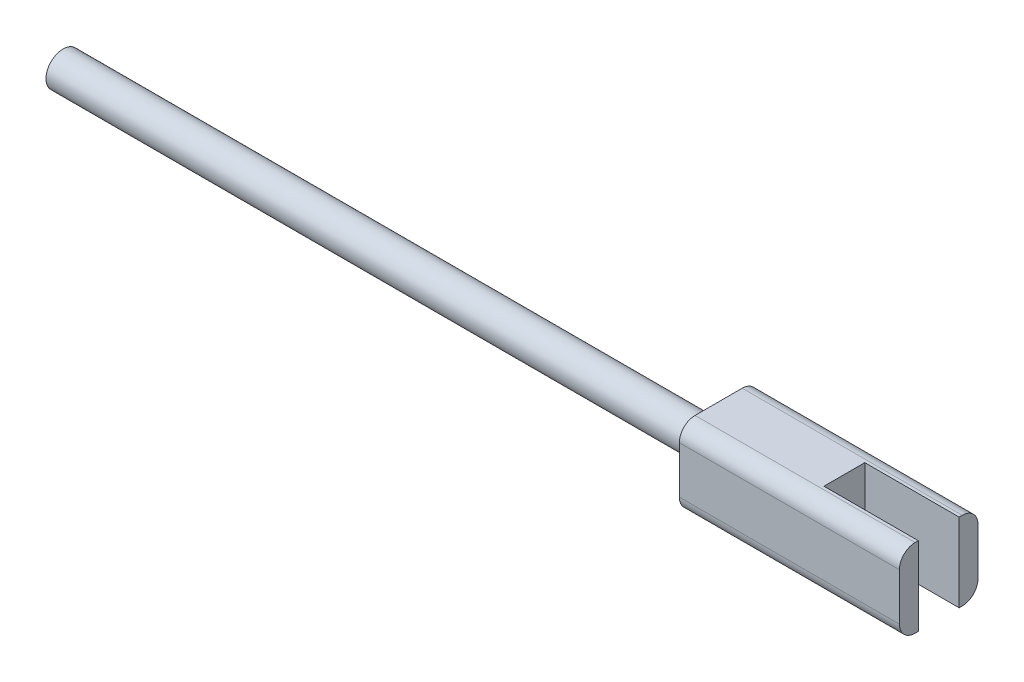
SolidWorks part; units mm, degrees
ref_plane "Front Plane" through (0, 0, 0) normal (0, 0, 1) x (1, 0, 0)
ref_plane "Top Plane" through (0, 0, 0) normal (0, 1, 0) x (1, 0, 0)
ref_plane "Right Plane" through (0, 0, 0) normal (1, 0, 0) x (0, 0, -1)
sketch "Sketch1" plane through (0, 0, 0) normal (1, 0, 0) x (0, 0, -1)
  circle A0 centre (0, 0) radius 1.09
extrude "Boss-Extrude1" add sketch "Sketch1" along normal blind 43.702
ref_plane "Plane1" through (41.702, 0, 0) normal (1, 0, 0) x (0, 0, -1)
sketch "Sketch2" plane through (41.702, 0, 0) normal (1, 0, 0) x (0, 0, -1)
  line L0 (-1.5, -2.5) -> (1.5, -2.5)
  line L1 (2.5, -1.5) -> (2.5, 1.5)
  line L2 (1.5, 2.5) -> (-1.5, 2.5)
  line L3 (-2.5, 1.5) -> (-2.5, -1.5)
  arc A0 (1.5, -2.5) -> (2.5, -1.5) centre (1.5, -1.5) ccw
  arc A1 (2.5, 1.5) -> (1.5, 2.5) centre (1.5, 1.5) ccw
  arc A2 (-1.5, 2.5) -> (-2.5, 1.5) centre (-1.5, 1.5) ccw
  arc A3 (-2.5, -1.5) -> (-1.5, -2.5) centre (-1.5, -1.5) ccw
extrude "Boss-Extrude2" add sketch "Sketch2" along normal blind 14
sketch "Sketch3" plane through (0, 0, 0) normal (0, 1, 0) x (1, 0, 0)
  line L0 (49.702, 1.3) -> (56.702, 1.3)
  line L1 (56.702, 1.3) -> (56.702, -1.3)
  line L2 (56.702, -1.3) -> (49.702, -1.3)
  line L3 (49.702, -1.3) -> (49.702, 1.3)
extrude "Cut-Extrude1" cut sketch "Sketch3" against normal through all and the other way through all
